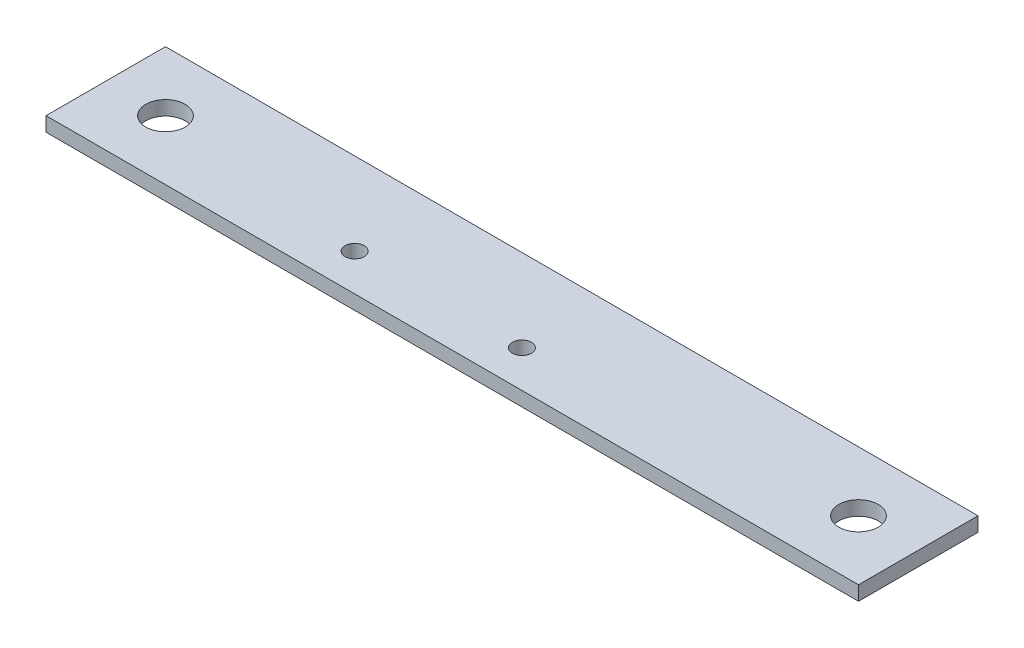
SolidWorks part; units mm, degrees
ref_plane "Front Plane" through (0, 0, 0) normal (0, 0, 1) x (1, 0, 0)
ref_plane "Top Plane" through (0, 0, 0) normal (0, 1, 0) x (1, 0, 0)
ref_plane "Right Plane" through (0, 0, 0) normal (1, 0, 0) x (0, 0, -1)
sketch "Sketch1" plane through (0, 0, 0) normal (0, 1, 0) x (1, 0, 0)
  line L1 (-85, 12.5) -> (85, 12.5)
  line L2 (-85, 12.5) -> (-85, -12.5)
  line L3 (-85, -12.5) -> (85, -12.5)
  line L4 (85, 12.5) -> (85, -12.5)
  line L5 (-85, 12.5) -> (85, -12.5) construction
  line L6 (-85, -12.5) -> (85, 12.5) construction
  circle A0 centre (-10.6801, 3.3392) radius 4.5
  circle A1 centre (-10.6585, -3.6607) radius 14
  circle A2 centre (-28.1585, -4.7634) radius 2
  circle A3 centre (6.8415, -4.7634) radius 2
  circle A4 centre (72.5, 0) radius 4.125
  point P0 (0, 0)
  point P17 (85, 0)
  dimension "D3" = 12.5
  dimension "D4" = 4
  dimension "D5" = 4
  dimension "D6" = 8.25
  dimension "D1" = 25
  dimension "D2" = 170
extrude "Boss-Extrude1" add sketch "Sketch1" along normal blind 3 contours A1 L3 L4 L1 L2 A4 A3 A2 | L3 A1 A0 | A0 region at (0, 0, -10.7817) region at (-10.6556, 0, 2.8007)
sketch "Sketch2" plane through (0, 3, 0) normal (0, 1, 0) x (1, 0, 0)
  line L0 (-85, 12.5) -> (-85, -12.5) construction
  circle A0 centre (-72.5, 0) radius 4.125
  circle A1 centre (-72.5, 0) radius 20 construction
  circle A2 centre (-42.5, 0) radius 10 construction
  dimension "D1" = 8.25
  dimension "D2" = 12.5
extrude "Cut-Extrude1" cut sketch "Sketch2" against normal through all
